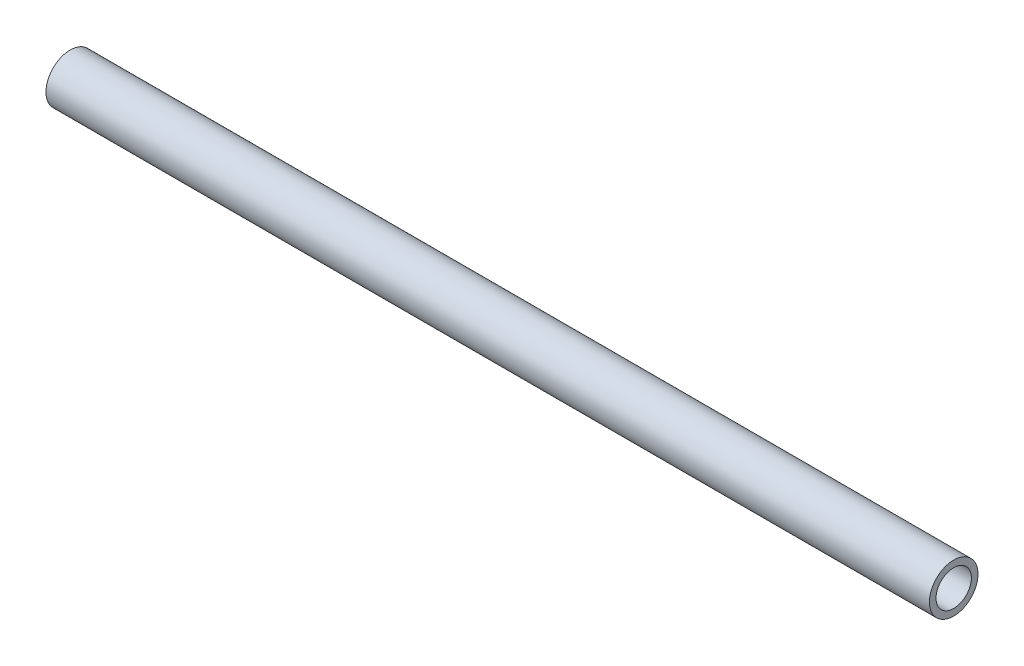
SolidWorks part; units mm, degrees
ref_plane "Front Plane" through (0, 0, 0) normal (0, 0, 1) x (1, 0, 0)
ref_plane "Top Plane" through (0, 0, 0) normal (0, 1, 0) x (1, 0, 0)
ref_plane "Right Plane" through (0, 0, 0) normal (1, 0, 0) x (0, 0, -1)
sketch "Sketch1" plane through (0, 0, 0) normal (1, 0, 0) x (0, 0, -1)
  circle A0 centre (0, 0) radius 4.125
  circle A1 centre (0, 0) radius 3
  dimension "D1" = 8.25
  dimension "D2" = 6
extrude "Boss-Extrude1" add sketch "Sketch1" along normal blind 150
